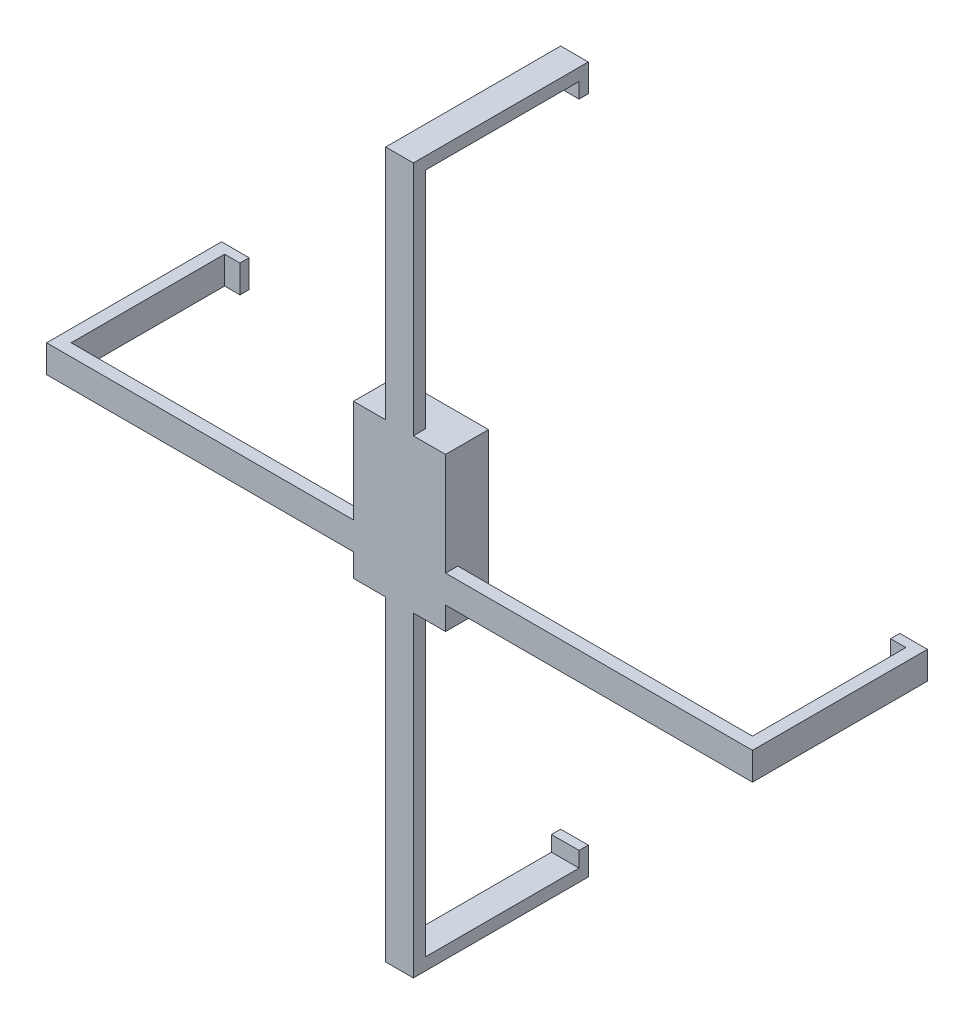
SolidWorks part; units mm, degrees
ref_plane "Front Plane" through (0, 0, 0) normal (0, 0, 1) x (1, 0, 0)
ref_plane "Top Plane" through (0, 0, 0) normal (0, 1, 0) x (1, 0, 0)
ref_plane "Right Plane" through (0, 0, 0) normal (1, 0, 0) x (0, 0, -1)
sketch "Sketch6" plane through (0, 0, 0) normal (1, 0, 0) x (0, 0, -1)
  line L8 (27.5, 60) -> (27.5, 55.5)
  line L10 (1, -53) -> (1, 58)
  line L12 (-1, -55) -> (-1, 60)
  line L13 (-1, -55) -> (27.5, -55)
  line L15 (1, -53) -> (26, -53)
  line L18 (27.5, -55) -> (27.5, -50.5)
  line L19 (27.5, -50.5) -> (26, -50.5)
  line L20 (26, -53) -> (26, -50.5)
  line L21 (27.5, 55.5) -> (26, 55.5)
  line L22 (-1, 60) -> (27.5, 60)
  line L24 (1, 58) -> (26, 58)
  line L26 (26, 58) -> (26, 55.5)
  point P27 (13.25, 60)
  dimension "D1" = 4.5
  dimension "D2" = 1.5
  dimension "D3" = 2
  dimension "D4" = 2
  dimension "D5" = 115
  dimension "D6" = 4.5
  dimension "D7" = 25
  dimension "D8" = 2
  dimension "D9" = 1.5
  dimension "D10" = 25
ref_plane "Plane2" through (0, 2.5, 0) normal (0, 1, 0) x (1, 0, 0)
sketch "Sketch8" plane through (0, 2.5, 0) normal (0, 1, 0) x (1, 0, 0)
  line L0 (-57.5, -1) -> (57.5, -1)
  line L1 (-55.5, 1) -> (55.5, 1)
  line L2 (53, 27.5) -> (53, 26)
  line L3 (57.5, -1) -> (57.5, 27.5)
  line L4 (53, 26) -> (55.5, 26)
  line L5 (-57.5, -1) -> (-57.5, 27.5)
  line L6 (-55.5, 1) -> (-55.5, 26)
  line L7 (-57.5, 27.5) -> (-53, 27.5)
  line L8 (55.5, 1) -> (55.5, 26)
  line L9 (-55.5, 26) -> (-53, 26)
  line L10 (-53, 27.5) -> (-53, 26)
  line L11 (53, 27.5) -> (57.5, 27.5)
  line L12 (0, -1) -> (0, 1) construction
  point P0 (10.2551, -12.9586)
  dimension "D1" = 115
  dimension "D2" = 4.5
  dimension "D3" = 4.5
  dimension "D4" = 2
  dimension "D5" = 2
  dimension "D6" = 1.5
  dimension "D7" = 1.5
  dimension "D8" = 25
  dimension "D9" = 2
  dimension "D10" = 25
extrude "Boss-Extrude7" add sketch "Sketch8" along normal blind 2.25 and the other way blind 2.25
sketch "Sketch10" plane through (0, 0, -1) normal (0, 0, -1) x (-1, 0, 0)
  line L0 (7.5, 21.5) -> (7.5, -3.5)
  line L1 (7.5, -3.5) -> (6.5, -3.5)
  line L2 (6.5, 20.5) -> (-6.5, 20.5)
  line L3 (6.5, 20.5) -> (6.5, -2.5)
  line L4 (-6.5, 20.5) -> (-6.5, -2.5)
  line L5 (-7.5, 21.5) -> (-7.5, -3.5)
  line L6 (7.5, 21.5) -> (-7.5, 21.5)
  line L7 (6.5, -2.5) -> (6.5, -3.5)
  line L8 (-6.5, -2.5) -> (-6.5, -3.5)
  line L9 (-6.5, -3.5) -> (-7.5, -3.5)
  point P6 (0, 1)
  dimension "D1" = 23
  dimension "D2" = 13
sketch "Sketch11" plane through (0, 0, -1) normal (0, 0, -1) x (-1, 0, 0)
  line L0 (-7.5, 21.5) -> (7.5, 21.5)
  line L1 (-7.5, 21.5) -> (-7.5, -3.5)
  line L2 (-7.5, -3.5) -> (7.5, -3.5)
  line L3 (7.5, 21.5) -> (7.5, -3.5)
extrude "Boss-Extrude10" add sketch "Sketch10" along normal blind 5
extrude "Boss-Extrude11" add sketch "Sketch11" against normal up to surface (2 mm away) up to face at (0, 2.5, 1)
extrude "Boss-Extrude12" add sketch "Sketch6" along normal blind 2.25 and the other way blind 2.25
